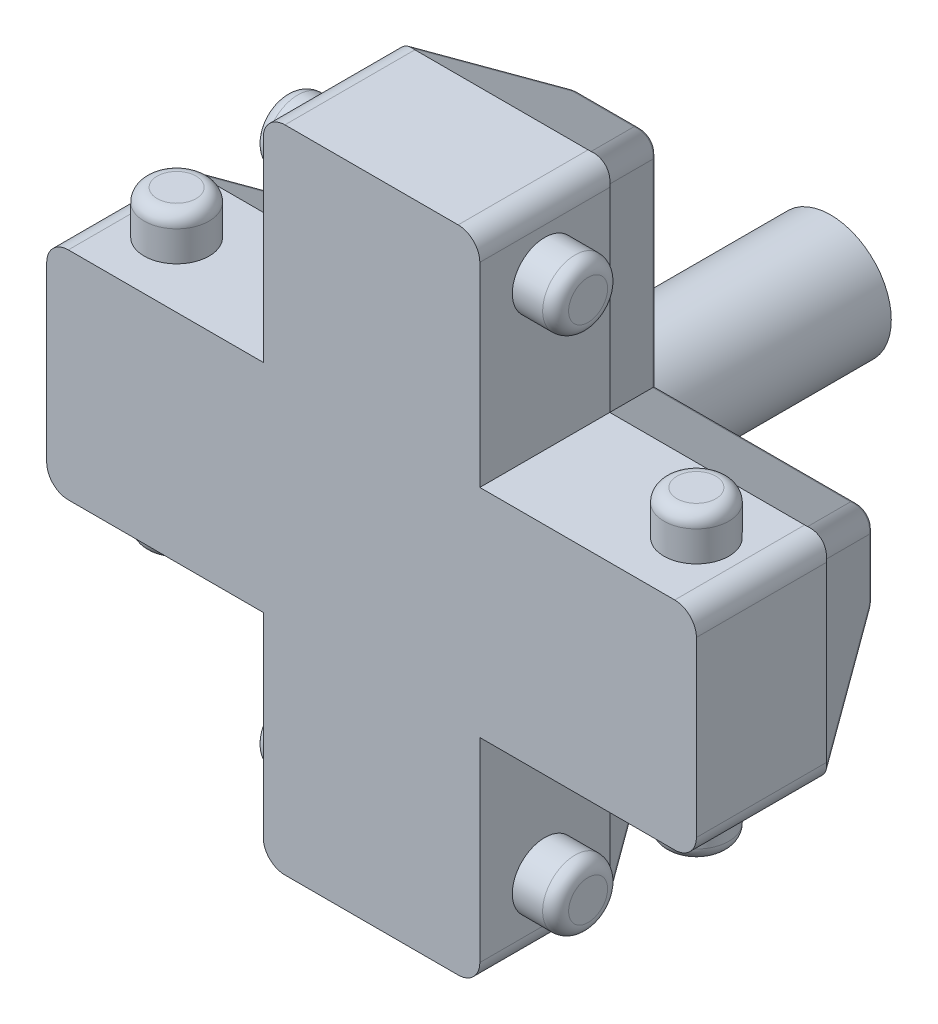
SolidWorks part; units mm, degrees
ref_plane "Front Plane" through (0, 0, 0) normal (0, 0, 1) x (1, 0, 0)
ref_plane "Top Plane" through (0, 0, 0) normal (0, 1, 0) x (1, 0, 0)
ref_plane "Right Plane" through (0, 0, 0) normal (1, 0, 0) x (0, 0, -1)
sketch "Sketch1" plane through (0, 0, 0) normal (0, 0, 1) x (1, 0, 0)
  circle A0 centre (0, 0) radius 14
  dimension "D1" = 28
extrude "Boss-Extrude1" add sketch "Sketch1" along normal blind 76
sketch "Sketch2" plane through (0, 0, 76) normal (0, 0, 1) x (1, 0, 0)
  line L1 (75, 25) -> (-75, 25)
  line L2 (75, 25) -> (75, -25)
  line L3 (75, -25) -> (-75, -25)
  line L4 (-75, 25) -> (-75, -25)
  line L5 (75, 25) -> (-75, -25) construction
  line L6 (75, -25) -> (-75, 25) construction
  line L7 (25, -75) -> (-25, -75)
  line L8 (25, -75) -> (25, 75)
  line L9 (25, 75) -> (-25, 75)
  line L10 (-25, -75) -> (-25, 75)
  line L11 (25, -75) -> (-25, 75) construction
  line L12 (25, 75) -> (-25, -75) construction
  point P0 (0, 0)
  point P6 (0, 0)
  circle M9 centre (0, 0) radius 14
  dimension "D1" = 150
  dimension "D2" = 150
  dimension "D3" = 50
  dimension "D4" = 50
extrude "Boss-Extrude2" add sketch "Sketch2" along normal blind 30 separate body contours L10 L1 L8 L9 | L8 L3 L2 L1 | L10 L7 L8 L3 | L3 L10 L1 L4 | L10 L3 L8 L1 M9 | M9 region at (50, 0, 76) region at (24.2929, 0, 76) region at (0, 50, 76) region at (-50, 0, 76) region at (0, -50, 76) region at (0, 0, 76)
ref_plane "Plane1" through (0, 0, 0) normal (-1, 0, 0) x (0, 0, 1)
sketch "Sketch4" plane through (0, 0, 0) normal (-1, 0, 0) x (0, 0, 1)
  line L0 (91, 75) -> (91, 25) construction
  line L1 (106, 75) -> (76, 75) construction
  line L2 (106, 25) -> (76, 25) construction
  line L3 (0, 0) -> (76, 0) construction
  line L4 (76, -14) -> (76, 14) construction
  circle A0 centre (91, 60) radius 7.5
  circle A1 centre (91, -60) radius 7.5
  dimension "D2" = 15
  dimension "D1" = 15
extrude "Boss-Extrude3" add sketch "Sketch4" along normal mid plane 70
sketch "Sketch5" plane through (0, 0, 0) normal (0, 1, 0) x (1, 0, 0)
  line L0 (-75, -91) -> (-25, -91) construction
  line L1 (-75, -106) -> (-75, -76) construction
  line L2 (-25, -106) -> (-25, -76) construction
  line L3 (0, 0) -> (0, -115.5475) construction
  line L4 (0, 16.5) -> (0, -16.5) construction
  circle A0 centre (-60, -91) radius 7.5
  circle A1 centre (60, -91) radius 7.5
  dimension "D2" = 15
  dimension "D1" = 15
extrude "Boss-Extrude4" add sketch "Sketch5" along normal mid plane 70
sketch "Sketch6" plane through (0, 0, 76) normal (0, 0, -1) x (-1, 0, 0)
  line L12 (25, 25) -> (25, 75)
  line L13 (25, 75) -> (-25, 75)
  line L14 (-25, 75) -> (-25, 25)
  line L15 (-25, 25) -> (-75, 25)
  line L16 (-75, 25) -> (-75, -25)
  line L17 (-75, -25) -> (-25, -25)
  line L18 (-25, -25) -> (-25, -75)
  line L19 (-25, -75) -> (25, -75)
  line L20 (25, -75) -> (25, -25)
  line L21 (25, -25) -> (75, -25)
  line L22 (75, -25) -> (75, 25)
  line L23 (75, 25) -> (25, 25)
  line L24 (25, 25) -> (25, 75)
  line L25 (25, 75) -> (-25, 75)
  line L26 (-25, 75) -> (-25, 25)
  line L27 (-25, 25) -> (-75, 25)
  line L28 (-75, 25) -> (-75, -25)
  line L29 (-75, -25) -> (-25, -25)
  line L30 (-25, -25) -> (-25, -75)
  line L31 (-25, -75) -> (25, -75)
  line L32 (25, -75) -> (25, -25)
  line L33 (25, -25) -> (75, -25)
  line L34 (75, -25) -> (75, 25)
  line L35 (75, 25) -> (25, 25)
  dimension "D1" = 0
extrude "Boss-Extrude5" add sketch "Sketch6" along normal blind 26 draft 30
fillet "Fillet1" radius 5 28 edges at (-75, 25, 91) (-75, -25, 91) (-25, -75, 91) (25, -75, 91) (75, -25, 91) (75, 25, 91) (25, 75, 91) (-25, 75, 91) (17.4944, 67.4944, 63) (-17.4944, 67.4944, 63) (-67.4944, 17.4944, 63) (-67.4944, -17.4944, 63) (-17.4944, -67.4944, 63) (17.4944, -67.4944, 63) (67.4944, -17.4944, 63) (67.4944, 17.4944, 63) (-59.9889, 0, 50) (-34.9889, -9.9889, 50) (-9.9889, -34.9889, 50) (0, -59.9889, 50) (9.9889, -34.9889, 50) (34.9889, -9.9889, 50) (59.9889, 0, 50) (34.9889, 9.9889, 50) (9.9889, 34.9889, 50) (0, 59.9889, 50) (-34.9889, 9.9889, 50) (-9.9889, 34.9889, 50)
fillet "Fillet2" radius 3 8 edges at (-60, -35, 98.5) (-35, -60, 83.5) (35, -60, 83.5) (60, -35, 83.5) (60, 35, 83.5) (35, 60, 98.5) (-35, 60, 98.5) (-60, 35, 98.5)
